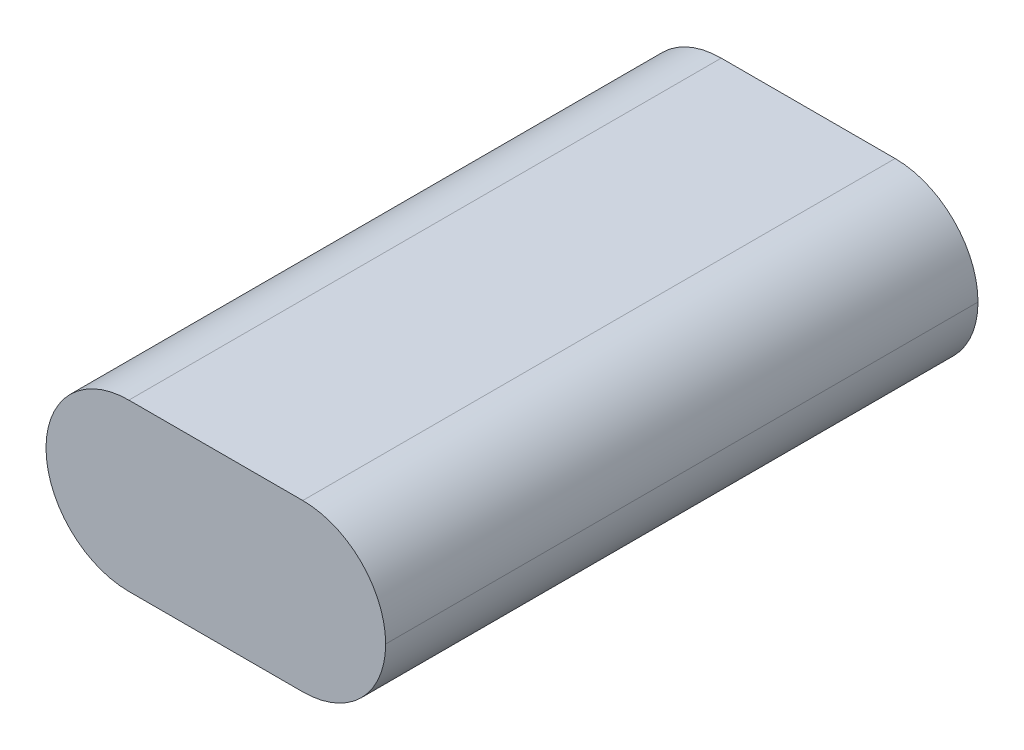
SolidWorks part; units mm, degrees
material "Nickel"
ref_plane "Front Plane" through (0, 0, 0) normal (0, 0, 1) x (1, 0, 0)
ref_plane "Top Plane" through (0, 0, 0) normal (0, 1, 0) x (1, 0, 0)
ref_plane "Right Plane" through (0, 0, 0) normal (1, 0, 0) x (0, 0, -1)
sketch "Sketch1" plane through (0, 0, 0) normal (0, 1, 0) x (1, 0, 0)
  line L1 (-18.75, 32.7) -> (18.75, 32.7)
  line L2 (-18.75, 32.7) -> (-18.75, -32.7)
  line L3 (-18.75, -32.7) -> (18.75, -32.7)
  line L4 (18.75, 32.7) -> (18.75, -32.7)
  line L5 (-18.75, 32.7) -> (18.75, -32.7) construction
  line L6 (-18.75, -32.7) -> (18.75, 32.7) construction
  point P0 (0, 0)
  dimension "D1" = 37.5
  dimension "D2" = 65.4
extrude "Boss-Extrude1" add sketch "Sketch1" along normal mid plane 18.3
fillet "Fillet1" radius 9.15 4 edges at (18.75, -9.15, 0) (18.75, 9.15, 0) (-18.75, -9.15, 0) (-18.75, 9.15, 0)
